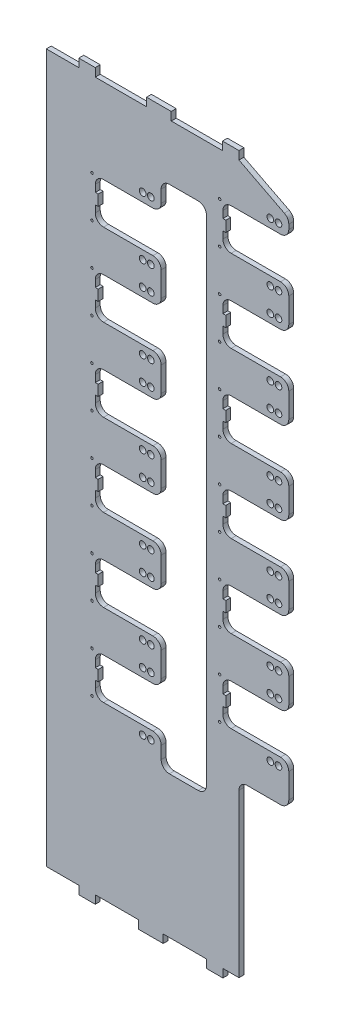
SolidWorks part; units mm, degrees
ref_plane "Płaszczyzna przednia" through (0, 0, 0) normal (0, 0, 1) x (1, 0, 0)
ref_plane "Płaszczyzna górna" through (0, 0, 0) normal (0, 1, 0) x (1, 0, 0)
ref_plane "Płaszczyzna prawa" through (0, 0, 0) normal (1, 0, 0) x (0, 0, -1)
sketch "Szkic1" plane through (0, 0, 0) normal (0, 0, 1) x (1, 0, 0)
  line L0 (-54.0228, 870) -> (-54.0228, 860)
  line L1 (-54.0228, 870) -> (-248.5228, 870)
  line L2 (6.4772, 822.853) -> (6.4772, 217.2374)
  line L5 (-54.0228, 860) -> (1.0418, 831.7504)
  line L9 (-54.0228, 197.2374) -> (-54.0228, -10)
  line L10 (-54.0228, -10) -> (-248.5228, -10)
  line L11 (-3.5228, 207.2374) -> (-44.0228, 207.2374)
  line L92 (-248.5228, 870) -> (-248.5228, -10)
  arc A0 (6.4772, 822.853) -> (1.0418, 831.7504) centre (-3.5228, 822.853) ccw
  arc A1 (6.4772, 217.2374) -> (-3.5228, 207.2374) centre (-3.5228, 217.2374) cw
  arc A2 (-44.0228, 207.2374) -> (-54.0228, 197.2374) centre (-44.0228, 197.2374) ccw
  dimension "D1" = 10
  dimension "D2" = 10
  dimension "D3" = 10
extrude "Dodanie-wyciągnięcie1" add sketch "Szkic1" against normal blind 6 separate body
sketch "Szkic8" plane through (0, 0, 0) normal (0, 0, 1) x (1, 0, 0)
  line L0 (-54.0228, 870) -> (-248.5228, 870) construction
  line L2 (-158.5228, 707.2374) -> (-218.5228, 707.2374)
  line L3 (-218.5228, 757.2374) -> (-158.5228, 757.2374)
  line L4 (-228.5228, 717.2374) -> (-228.5228, 747.2374)
  line L5 (-148.5228, 767.2374) -> (-148.5228, 697.2374)
  line L9 (6.4772, 217.2374) -> (6.4772, 822.853) construction
  arc A2 (-148.5228, 697.2374) -> (-158.5228, 707.2374) centre (-158.5228, 697.2374) ccw
  arc A3 (-158.5228, 757.2374) -> (-148.5228, 767.2374) centre (-158.5228, 767.2374) ccw
  arc A4 (-218.5228, 707.2374) -> (-228.5228, 717.2374) centre (-218.5228, 717.2374) cw
  arc A5 (-218.5228, 757.2374) -> (-228.5228, 747.2374) centre (-218.5228, 747.2374) ccw
  dimension "D4" = 10
  dimension "D5" = 10
  dimension "D7" = 10
  dimension "D2" = 155
  dimension "D3" = 50
  dimension "D6" = 80
  dimension "D8" = 112.7626
extrude "Wytnij-wyciągnięcie4" cut sketch "Szkic8" against normal through all
sketch "Szkic7" plane through (0, 0, 0) normal (0, 0, 1) x (1, 0, 0)
  line L0 (-225.0228, 726.9874) -> (-225.0228, 737.4874)
  line L1 (-228.5228, 738.7374) -> (-225.0228, 738.7374)
  line L2 (-228.5228, 738.7374) -> (-228.5228, 736.7374)
  line L3 (-228.5228, 725.7374) -> (-225.0228, 725.7374)
  line L4 (-225.0228, 738.7374) -> (-225.0228, 737.4874)
  line L7 (-225.0228, 726.9874) -> (-225.0228, 725.7374)
  line L8 (-228.5228, 727.7374) -> (-228.5228, 725.7374)
  line L9 (-158.5228, 757.2374) -> (-218.5228, 757.2374) construction
  line L10 (-228.5228, 727.7374) -> (-228.5228, 736.7374)
  point P10 (-228.5228, 732.2374)
  dimension "D1" = 3.5
  dimension "D2" = 13
  dimension "D3" = 1.25
  dimension "D4" = 1.25
  dimension "D5" = 2
  dimension "D6" = 2
  dimension "D7" = 25
  dimension "D8" = 6.5
extrude "Dodanie-wyciągnięcie2" add sketch "Szkic7" against normal blind 6
sketch "Szkic5" plane through (0, 0, 0) normal (0, 0, 1) x (1, 0, 0)
  circle A0 centre (-232.5228, 707.2374) radius 1.5 construction
  circle A1 centre (-232.5228, 757.2374) radius 1.5 construction
  circle A2 centre (-232.5228, 707.2374) radius 1.5
  circle A3 centre (-232.5228, 757.2374) radius 1.5
extrude "Wytnij-wyciągnięcie2" cut sketch "Szkic5" against normal blind 6
pattern_linear "Szyk liniowy4" count 2 spacing 155 along (1, 0, 0) count 2 spacing 50 along (0, 1, 0) skipping (0, 1), (1, 0) of "Wytnij-wyciągnięcie4", "Dodanie-wyciągnięcie2", "Wytnij-wyciągnięcie2"
pattern_linear "Szyk liniowy3" count 6 spacing 100 along (0, -1, 0) of "Dodanie-wyciągnięcie2", "Wytnij-wyciągnięcie4", "Szyk liniowy4", "Wytnij-wyciągnięcie2"
sketch "Szkic2" plane through (0, 0, 0) normal (0, 0, 1) x (1, 0, 0)
  line L0 (-166.2728, 870) -> (-166.2728, 859.95)
  line L1 (-166.2728, 870) -> (-228.5228, 870)
  line L2 (-166.2728, 859.95) -> (-228.5228, 859.95)
  line L3 (-228.5228, 870) -> (-228.5228, 859.95)
  line L4 (-54.0228, 870) -> (-248.5228, 870) construction
  line L5 (-248.5228, 870) -> (-248.5228, -10) construction
  line L7 (-74.0228, 870) -> (-136.2728, 870)
  line L8 (-136.2728, 870) -> (-136.2728, 859.95)
  line L9 (-136.2728, 859.95) -> (-74.0228, 859.95)
  line L10 (-74.0228, 859.95) -> (-74.0228, 870)
  dimension "D1" = 10.05
  dimension "D2" = 0
  dimension "D3" = 20
  dimension "D6" = 10.05
  dimension "D7" = 62.25
extrude "Wytnij-wyciągnięcie1" cut sketch "Szkic2" against normal blind 6
sketch "Szkic10" plane through (0, 0, 0) normal (0, 0, 1) x (1, 0, 0)
  line L0 (-103.5228, 792.2374) -> (-138.5228, 792.2374)
  line L1 (-93.5228, 782.2374) -> (-93.5228, 182.2374)
  line L2 (-148.5228, 782.2374) -> (-148.5228, 182.2374)
  line L3 (-103.5228, 172.2374) -> (-138.5228, 172.2374)
  line L6 (-158.5228, 757.2374) -> (-218.5228, 757.2374) construction
  line L7 (-218.5228, 207.2374) -> (-158.5228, 207.2374) construction
  line L8 (6.4772, 717.2374) -> (6.4772, 747.2374) construction
  arc A0 (-138.5228, 792.2374) -> (-148.5228, 782.2374) centre (-138.5228, 782.2374) ccw
  arc A1 (-93.5228, 782.2374) -> (-103.5228, 792.2374) centre (-103.5228, 782.2374) ccw
  arc A2 (-93.5228, 182.2374) -> (-103.5228, 172.2374) centre (-103.5228, 182.2374) cw
  arc A3 (-148.5228, 182.2374) -> (-138.5228, 172.2374) centre (-138.5228, 182.2374) ccw
  dimension "D6" = 10
  dimension "D1" = 35
  dimension "D2" = 55
  dimension "D3" = 35
  dimension "D4" = 35
  dimension "D5" = 100
extrude "Wytnij-wyciągnięcie5" cut sketch "Szkic10" against normal through all
sketch "Szkic6" plane through (0, 0, 0) normal (0, 0, 1) x (1, 0, 0)
  line L1 (-228.5228, -10) -> (-176.0228, -10)
  line L2 (-228.5228, -10) -> (-228.5228, 0.05)
  line L3 (-228.5228, 0.05) -> (-176.0228, 0.05)
  line L4 (-176.0228, -10) -> (-176.0228, 0.05)
  line L5 (-248.5228, 870) -> (-248.5228, -10) construction
  line L8 (-248.5228, -10) -> (-54.0228, -10) construction
  line L9 (-146.0228, -10) -> (-93.5228, -10)
  line L10 (-146.0228, -10) -> (-146.0228, 0.05)
  line L11 (-93.5228, -10) -> (-93.5228, 0.05)
  line L12 (-146.0228, 0.05) -> (-93.5228, 0.05)
  line L16 (-54.0228, -10) -> (-73.5228, -10)
  line L17 (-54.0228, -10) -> (-54.0228, 0.05)
  line L18 (-73.5228, -10) -> (-73.5228, 0.05)
  line L19 (-54.0228, 0.05) -> (-73.5228, 0.05)
  line L20 (-54.0228, -10) -> (-54.0228, 197.2374) construction
  dimension "D1" = 10.05
  dimension "D2" = 20
  dimension "D3" = 10.05
  dimension "D4" = 0
  dimension "D5" = 30
  dimension "D6" = 19.5
  dimension "D7" = 20
  dimension "D8" = 10.05
  dimension "D9" = 52.5
extrude "Wytnij-wyciągnięcie3" cut sketch "Szkic6" against normal through all
sketch "Szkic11" plane through (0, 0, 0) normal (0, 0, 1) x (1, 0, 0)
  line L0 (-248.5228, 859.95) -> (-288.0228, 859.95)
  line L1 (-248.5228, 859.95) -> (-248.5228, 0.05)
  line L2 (-288.0228, 859.95) -> (-288.0228, 0.05)
  line L3 (-248.5228, 0.05) -> (-288.0228, 0.05)
  line L4 (-288.0228, 859.9) -> (-288.0228, 175) construction
  line L5 (-228.5228, 859.95) -> (-166.2728, 859.95) construction
  line L7 (-176.0228, 0.05) -> (-228.5228, 0.05) construction
  dimension "D1" = 0
  dimension "D2" = 0
  dimension "D3" = 0
extrude "Dodanie-wyciągnięcie3" add sketch "Szkic11" against normal blind 6
sketch "Szkic12" plane through (0, 0, 0) normal (0, 0, 1) x (1, 0, 0)
  line L16 (-18.5228, 315.2374) -> (-13.5228, 315.2374)
  line L17 (-13.5228, 320.2374) -> (-18.5228, 320.2374)
  line L18 (-18.5228, 320.2374) -> (-18.5228, 315.2374)
  line L19 (-13.5228, 315.2374) -> (-13.5228, 320.2374)
  line L20 (-8.5228, 320.2374) -> (-8.5228, 315.2374)
  line L21 (-8.5228, 315.2374) -> (-3.5228, 315.2374)
  line L22 (-3.5228, 320.2374) -> (-8.5228, 320.2374)
  line L23 (-3.5228, 315.2374) -> (-3.5228, 320.2374)
  line L24 (-8.5228, 244.2374) -> (-3.5228, 244.2374)
  line L25 (-8.5228, 249.2374) -> (-8.5228, 244.2374)
  line L26 (-3.5228, 249.2374) -> (-8.5228, 249.2374)
  line L27 (-3.5228, 244.2374) -> (-3.5228, 249.2374)
  line L28 (-13.5228, 244.2374) -> (-13.5228, 249.2374)
  line L29 (-18.5228, 244.2374) -> (-13.5228, 244.2374)
  line L30 (-18.5228, 249.2374) -> (-18.5228, 244.2374)
  line L31 (-13.5228, 249.2374) -> (-18.5228, 249.2374)
  line L32 (-16.0228, 315.2374) -> (-16.0228, 320.2374)
  line L33 (-13.5228, 317.7374) -> (-18.5228, 317.7374)
  line L34 (-6.0228, 315.2374) -> (-6.0228, 320.2374)
  line L35 (-3.5228, 317.7374) -> (-8.5228, 317.7374)
  line L36 (-8.5228, 246.7374) -> (-3.5228, 246.7374)
  line L37 (-6.0228, 244.2374) -> (-6.0228, 249.2374)
  line L38 (-16.0228, 244.2374) -> (-16.0228, 249.2374)
  line L39 (-18.5228, 246.7374) -> (-13.5228, 246.7374)
sketch "Szkic13" plane through (0, 0, 0) normal (0, 0, 1) x (1, 0, 0)
  line L0 (-16.0228, 315.2374) -> (-16.0228, 320.2374) construction
  line L1 (-6.0228, 315.2374) -> (-6.0228, 320.2374) construction
  line L2 (-16.0228, 244.2374) -> (-16.0228, 249.2374) construction
  line L3 (-8.5228, 246.7374) -> (-3.5228, 246.7374) construction
  circle A1 centre (-6.0228, 317.7374) radius 4.05
  circle A2 centre (-16.0228, 246.7374) radius 4.05
  circle A3 centre (-6.0228, 246.7374) radius 4.05
  circle A4 centre (-16.0228, 317.7374) radius 4.05
  dimension "D1" = 8.1
  dimension "D2" = 8.1
  dimension "D3" = 8.1
  dimension "D4" = 8.1
extrude "Wytnij-wyciągnięcie6" cut sketch "Szkic13" against normal blind 10
pattern_linear "Szyk liniowy6" count 2 spacing 155 along (1, 0, 0) count 2 spacing 50 along (0, 1, 0) of "Wytnij-wyciągnięcie6"
pattern_linear "Szyk liniowy7" count 6 spacing 100 along (0, 1, 0) of "Szyk liniowy6", "Wytnij-wyciągnięcie6"
